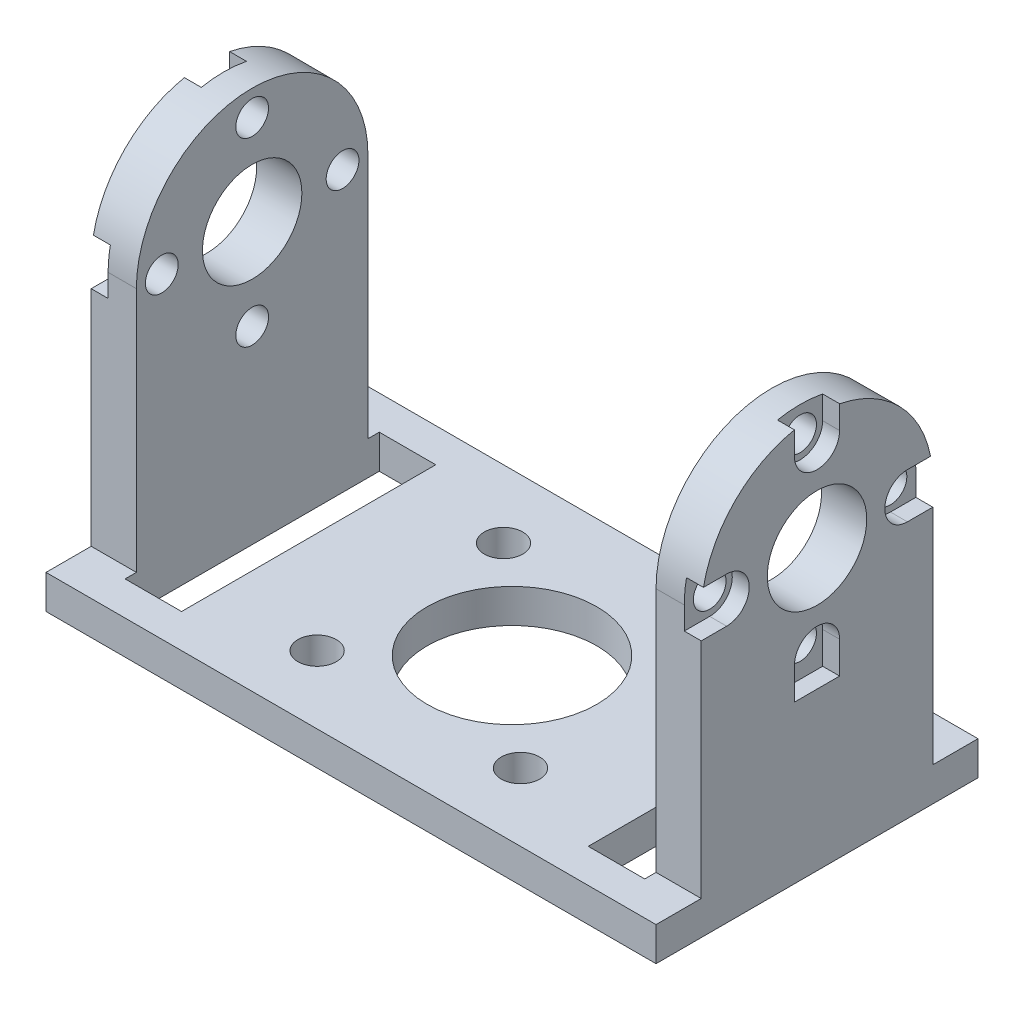
SolidWorks part; units mm, degrees
ref_plane "Front Plane" through (0, 0, 0) normal (0, 0, 1) x (1, 0, 0)
ref_plane "Top Plane" through (0, 0, 0) normal (0, 1, 0) x (1, 0, 0)
ref_plane "Right Plane" through (0, 0, 0) normal (1, 0, 0) x (0, 0, -1)
sketch "Sketch1" plane through (0, 0, 0) normal (0, 1, 0) x (1, 0, 0)
  line L0 (0, 0) -> (0, -7.6155) construction
  line L1 (-18, 14.25) -> (18, 14.25)
  line L2 (-18, 14.25) -> (-18, -14.25)
  line L3 (-18, -14.25) -> (18, -14.25)
  line L4 (18, 14.25) -> (18, -14.25)
  line L5 (0, 0) -> (0, 12.9892) construction
  line L6 (-18, 14.25) -> (-27, 14.25)
  line L7 (-18, 14.25) -> (-18, -14.25)
  line L8 (-18, -14.25) -> (-27, -14.25)
  line L9 (-27, 14.25) -> (-27, -14.25)
  line L10 (18, 14.25) -> (27, 14.25)
  line L11 (18, 14.25) -> (18, -14.25)
  line L12 (18, -14.25) -> (27, -14.25)
  line L13 (27, 14.25) -> (27, -14.25)
  line L14 (-23, 11.25) -> (-18, 11.25)
  line L15 (-23, 11.25) -> (-23, -11.25)
  line L16 (-23, -11.25) -> (-18, -11.25)
  line L17 (-18, 11.25) -> (-18, -11.25)
  line L18 (18, 11.25) -> (18, -11.25)
  line L19 (23, -11.25) -> (18, -11.25)
  line L20 (23, 11.25) -> (23, -11.25)
  line L21 (23, 11.25) -> (18, 11.25)
  circle A0 centre (0, 0) radius 7.5
  circle A1 centre (-9, 8.25) radius 1.7
  circle A2 centre (-9, -8.25) radius 1.7
  circle A3 centre (9, -8.25) radius 1.7
  circle A4 centre (9, 8.25) radius 1.7
  point P0 (0, 0)
  dimension "D3" = 9
  dimension "D4" = 8.25
  dimension "D5" = 8.25
  dimension "D6" = 9
  dimension "D7" = 9
  dimension "D9" = 15
  dimension "D1" = 36
  dimension "D2" = 28.5
  dimension "D8" = 9
  dimension "D10" = 4
  dimension "D11" = 3
  dimension "D12" = 3
  dimension "D13" = 5
extrude "Boss-Extrude2" add sketch "Sketch1" along normal blind 3 contours L6 L9 L8 L2 | L13 L10 L4 L12 | L4 L1 L2 L3 A3 A2 A1 A0 A4 region at (0, 0, -13.7908) region at (-24.0625, 0, 0) region at (24.0625, 0, 0)
sketch "Sketch2" plane through (0, 3, 0) normal (0, 1, 0) x (1, 0, 0)
  line L5 (27, 14.25) -> (27, -14.25) construction
  line L6 (27, 10.25) -> (23, 10.25)
  line L7 (27, 10.25) -> (27, -10.25)
  line L8 (27, -10.25) -> (23, -10.25)
  line L9 (23, 10.25) -> (23, -10.25)
  line L10 (27, 14.25) -> (-27, 14.25) construction
  dimension "D1" = 4
  dimension "D2" = 20.5
  dimension "D3" = 4
extrude "Boss-Extrude3" add sketch "Sketch2" along normal blind 21.75
sketch "Sketch4" plane through (27, 0, 0) normal (1, 0, 0) x (0, 0, -1)
  line L0 (-10.25, 24.75) -> (10.25, 24.75) construction
  circle A0 centre (0, 24.75) radius 10.25
  point P18 (0, 17.75)
  line M5 (10.25, 24.75) -> (-10.25, 24.75)
extrude "Boss-Extrude4" add sketch "Sketch4" against normal blind 4 contours A0 M5 | M5 | M5 | A0 M5 region at (27, 29.1002, 0) region at (27, 20.3998, 0)
ref_plane "Plane1" through (0, 0, 0) normal (1, 0, 0) x (0, 0, -1)
mirror "Mirror1" about plane through (0, 0, 0) normal (1, 0, 0) of "Boss-Extrude3", "Boss-Extrude4"
sketch "Sketch6" plane through (27, 0, 0) normal (1, 0, 0) x (0, 0, -1)
  line L0 (-10.25, 24.75) -> (10.25, 24.75) construction
  line L1 (0, 35) -> (0, 14.5) construction
  circle A6 centre (0, 24.75) radius 4.4
  circle A7 centre (0, 24.75) radius 8
  circle A8 centre (0, 32.75) radius 1.45
  circle A9 centre (8, 24.75) radius 1.45
  circle A10 centre (0, 16.75) radius 1.45
  circle A11 centre (-8, 24.75) radius 1.45
  circle A12 centre (0, 24.75) radius 10.25
  point P21 (0, 24.75)
  dimension "D1" = 8.8
  dimension "D2" = 16
  dimension "D3" = 4
  dimension "D4" = 2.9
extrude "Cut-Extrude3" cut sketch "Sketch6" against normal blind 4 contours A6 | A7 A11 | A7 A11 | A7 A10 | A7 A10 | A7 A9 | A7 A9 | A7 A8 | A7 A8 region at (27, 24.75, 0) region at (27, 24.75, -7.3615) region at (27, 24.75, -8.5911) region at (27, 32.1115, 0) region at (27, 33.3411, 0) region at (27, 16.1589, 0) region at (27, 17.3885, 0) region at (27, 24.75, 7.3615) region at (27, 24.75, 8.5911)
mirror "Mirror3" about plane through (0, 0, 0) normal (1, 0, 0) of "Cut-Extrude3"
sketch "Sketch7" plane through (27, 0, 0) normal (1, 0, 0) x (0, 0, -1)
  line L0 (10.8224, 26.75) -> (10.8224, 22.75)
  line L2 (-2, 32.75) -> (-2, 35.5724)
  line L3 (-2, 35.5724) -> (2, 35.5724)
  line L4 (2, 32.75) -> (2, 35.5724)
  line L5 (8, 22.75) -> (10.8224, 22.75)
  line L6 (8, 26.75) -> (10.8224, 26.75)
  line L7 (2, 13.9276) -> (-2, 13.9276)
  line L8 (-2, 16.75) -> (-2, 13.9276)
  line L9 (2, 16.75) -> (2, 13.9276)
  line L10 (-10.8224, 22.75) -> (-10.8224, 26.75)
  line L11 (-8, 26.75) -> (-10.8224, 26.75)
  line L12 (-8, 22.75) -> (-10.8224, 22.75)
  circle A0 centre (0, 32.75) radius 2
  circle A1 centre (0, 24.75) radius 8
  circle A2 centre (8, 24.75) radius 2
  circle A3 centre (0, 16.75) radius 2
  circle A4 centre (-8, 24.75) radius 2
  point P15 (0, 24.75)
  point P32 (0, 24.75)
  circle M1 centre (-8, 24.75) radius 1.45
  circle M2 centre (0, 16.75) radius 1.45
  circle M3 centre (8, 24.75) radius 1.45
  circle M4 centre (0, 32.75) radius 1.45
  line M6 (10.25, 3) -> (10.25, 24.75)
  arc M7 (10.25, 24.75) -> (-10.25, 24.75) centre (0, 24.75) ccw
  line M8 (-10.25, 24.75) -> (-10.25, 3)
  dimension "D1" = 4
  dimension "D3" = 4
  dimension "D2" = 4
  dimension "D4" = 4
extrude "Cut-Extrude4" cut sketch "Sketch7" against normal blind 1.5 contours A1 M1 | A1 M1 | A1 A0 M4 | A0 A1 M4 | A1 A2 M3 | A1 A2 M3 | A1 A3 M2 | A1 A3 M2 | L4 L3 L2 M7 | A0 L4 L2 M7 | A2 L5 L6 M6 M7 | A3 L8 L7 L9 | A4 L11 L12 M7 M8 | A4 region at (27, 25.7503, -10.155) region at (27, 26.1318, -9.3818) region at (27, 35.2508, 0) region at (27, 33.7765, -1.9541) region at (27, 26.4558, -7.7711) region at (27, 32.6276, -1.9503) region at (27, 30.7939, 0) region at (27, 26.7041, 9.0265) region at (27, 16.8724, -1.9503) region at (27, 16.9789, -1.7058) region at (27, 14.633, 0) region at (27, 24.75, 7.3615) region at (27, 24.75, 8.5911)
mirror "Mirror4" about plane through (0, 0, 0) normal (1, 0, 0) of "Cut-Extrude4"
